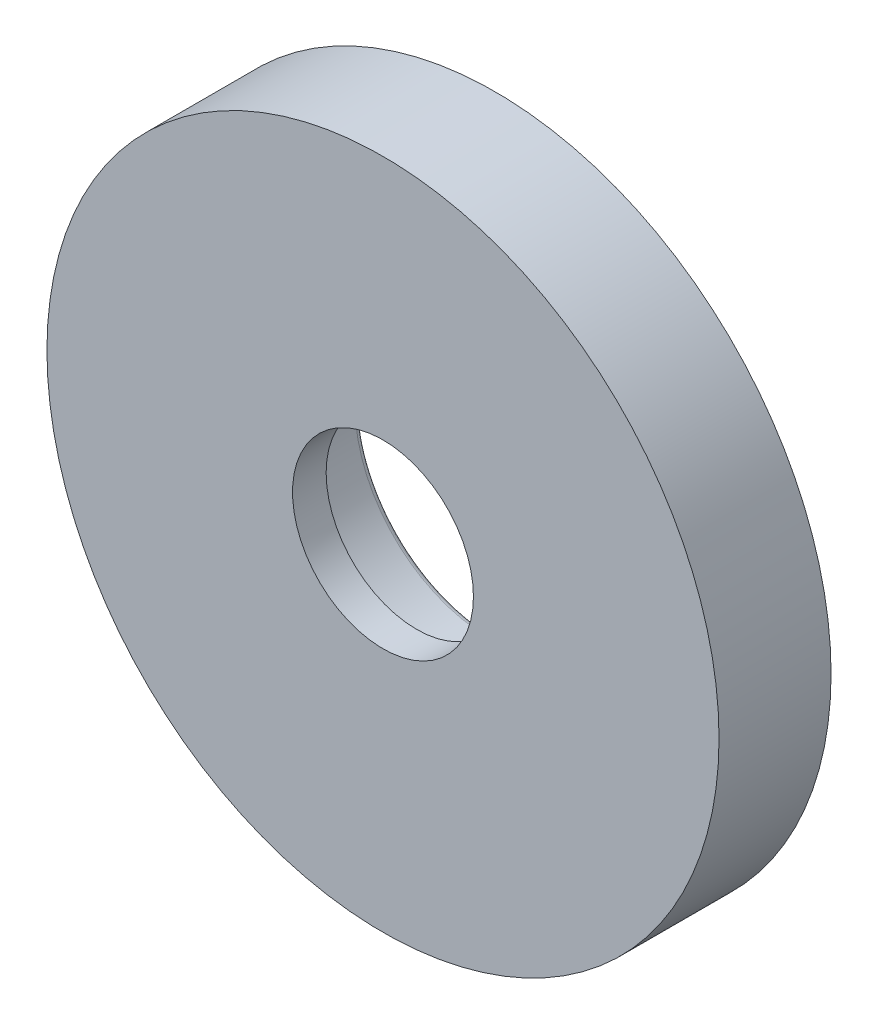
SolidWorks part; units mm, degrees
ref_plane "Front Plane" through (0, 0, 0) normal (0, 0, 1) x (1, 0, 0)
ref_plane "Top Plane" through (0, 0, 0) normal (0, 1, 0) x (1, 0, 0)
ref_plane "Right Plane" through (0, 0, 0) normal (1, 0, 0) x (0, 0, -1)
sketch "Sketch1" plane through (0, 0, 0) normal (0, 0, 1) x (1, 0, 0)
  line L0 (-6.7696, 13.9075) -> (-6.7696, 8.9075)
  line L1 (-6.7696, 13.9075) -> (6.7696, 13.9075) construction
  line L2 (-6.7696, 13.9075) -> (-6.7696, 8.9075) construction
  line L3 (-6.7696, 8.9075) -> (6.7696, 8.9075) construction
  line L4 (6.7696, 13.9075) -> (6.7696, 8.9075) construction
  line L5 (-6.7696, 13.9075) -> (6.7696, 8.9075) construction
  line L6 (-6.7696, 8.9075) -> (6.7696, 13.9075) construction
  line L7 (-2.3565, 13.9075) -> (2.3565, 13.9075) construction
  line L8 (6.7696, 11.6318) -> (6.7696, 9.9075) construction
  line L9 (-6.7696, 8.9075) -> (6.7696, 8.9075)
  line L10 (-5.7696, 8.9075) -> (5.7696, 8.9075) construction
  line L11 (6.7696, 13.9075) -> (6.7696, 8.9075)
  line L12 (-6.7696, 13.9075) -> (6.7696, 13.9075)
  circle A0 centre (0, 0) radius 15
  circle A1 centre (0, 0) radius 14.125
  point P3 (0, 11.4075)
  dimension "D1" = 30
  dimension "D2" = 28.25
  dimension "D3" = 0
extrude "Boss-Extrude1" add sketch "Sketch1" along normal blind 5 contours A0
extrude "Cut-Extrude1" cut sketch "Sketch1<5>" along normal blind 3.125 contours L4 A1 L1 L2 L3 region at (0, 11.2322, 0)
sketch "Sketch1<5>" plane through (0, 0, 0) normal (0, 0, 1) x (1, 0, 0) same geometry as "Sketch1"
sketch "Sketch7" plane through (0, 0, 3.125) normal (0, 0, -1) x (-1, 0, 0)
  line L8 (-6.6446, 12.3227) -> (-6.6446, 9.0325)
  line L9 (-6.6446, 9.0325) -> (6.6446, 9.0325)
  line L10 (6.6446, 9.0325) -> (6.6446, 12.3227)
  line L11 (2.4582, 13.7825) -> (-2.4582, 13.7825)
  line L12 (-6.6446, 12.3227) -> (-6.6446, 9.0325)
  line L13 (-6.6446, 9.0325) -> (6.6446, 9.0325)
  line L14 (6.6446, 9.0325) -> (6.6446, 12.3227)
  line L15 (2.4582, 13.7825) -> (-2.4582, 13.7825)
  arc A4 (6.6446, 12.3227) -> (2.4582, 13.7825) centre (0, 0) ccw
  arc A5 (-2.4582, 13.7825) -> (-6.6446, 12.3227) centre (0, 0) ccw
  arc A6 (6.6446, 12.3227) -> (2.4582, 13.7825) centre (0, 0) ccw
  arc A7 (-2.4582, 13.7825) -> (-6.6446, 12.3227) centre (0, 0) ccw
  line M7 (-6.7696, 12.3971) -> (-6.7696, 8.9075)
  line M8 (-6.7696, 8.9075) -> (6.7696, 8.9075)
  line M9 (6.7696, 8.9075) -> (6.7696, 12.3971)
  arc M10 (6.7696, 12.3971) -> (2.4692, 13.9075) centre (0, 0) ccw
  line M11 (2.4692, 13.9075) -> (-2.4692, 13.9075)
  arc M12 (-2.4692, 13.9075) -> (-6.7696, 12.3971) centre (0, 0) ccw
  dimension "D1" = 0.125
extrude "Boss-Extrude4" add sketch "Sketch7" along normal blind 3.125 contours A7 L15 A6 L14 L13 L12 M12 M7 M8 M9 M10 M11 region at (4.676, 13.3133, 3.125)
ref_axis "Axis1" through (0, 0, -0.25) along (0, 0, 1)
pattern_circular "CirPattern1" count 4 over 360 about axis through (0, 0, -0.25) along (0, 0, 1) of "Cut-Extrude1", "Boss-Extrude4"
sketch "Sketch4" plane through (0, 0, 0) normal (0, 0, -1) x (-1, 0, 0)
  circle A0 centre (0, 0) radius 6
  dimension "D1" = 12
extrude "Cut-Extrude2" cut sketch "Sketch4" against normal blind 3.5
fillet "Fillet1" radius 0.25 1 edges at (-6, 0, 0)
sketch "Sketch5" plane through (0, 0, 5) normal (0, 0, 1) x (1, 0, 0)
  circle A0 centre (0, 0) radius 4.0375
  dimension "D1" = 8.075
extrude "Cut-Extrude3" cut sketch "Sketch5" against normal through all both and the other way through all
fillet "Fillet2" radius 0.5 24 edges at (12.3227, -6.6446, 1.5625) (9.0325, -6.6446, 1.5625) (9.0325, 6.6446, 1.5625) (12.3227, 6.6446, 1.5625) (13.7825, 2.4582, 1.5625) (13.7825, -2.4582, 1.5625) (-6.6446, -12.3227, 1.5625) (-6.6446, -9.0325, 1.5625) (6.6446, -9.0325, 1.5625) (6.6446, -12.3227, 1.5625) (2.4582, -13.7825, 1.5625) (-2.4582, -13.7825, 1.5625) (-12.3227, 6.6446, 1.5625) (-9.0325, 6.6446, 1.5625) (-9.0325, -6.6446, 1.5625) (-12.3227, -6.6446, 1.5625) (-13.7825, -2.4582, 1.5625) (-13.7825, 2.4582, 1.5625) (6.6446, 9.0325, 1.5625) (-6.6446, 9.0325, 1.5625) (-6.6446, 12.3227, 1.5625) (-2.4582, 13.7825, 1.5625) (2.4582, 13.7825, 1.5625) (6.6446, 12.3227, 1.5625)
